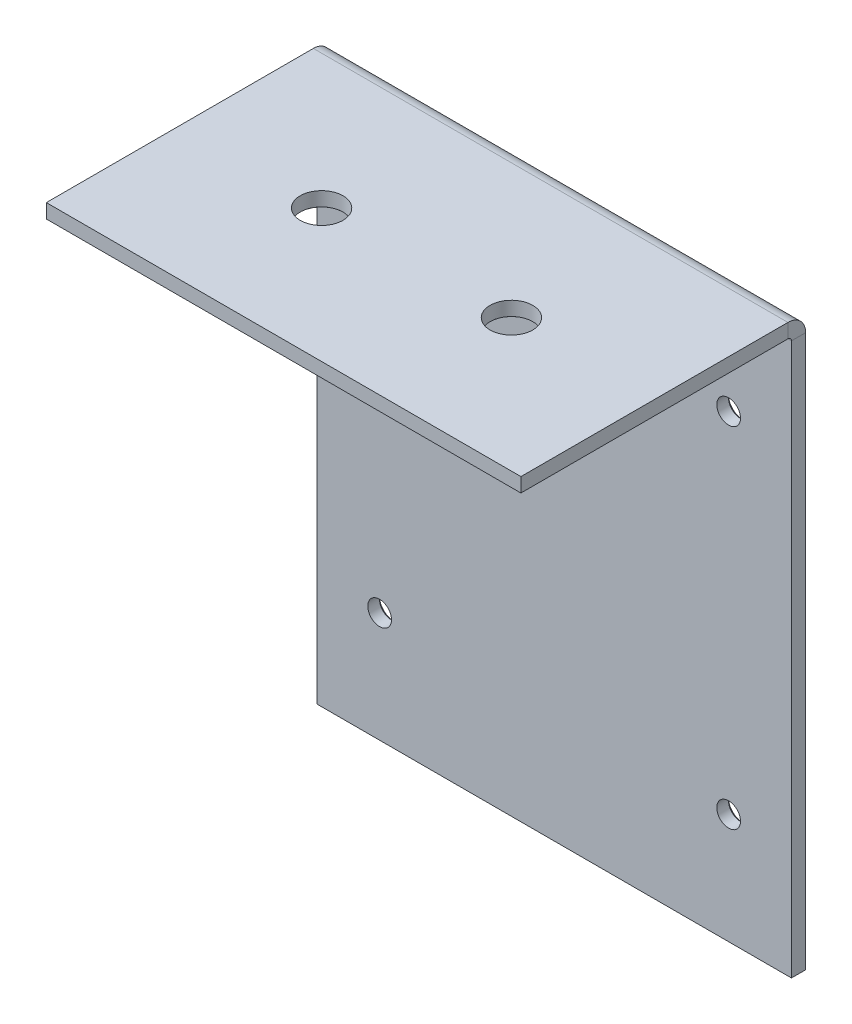
SolidWorks part; units mm, degrees
note: The reader was unsure of these and kept them because the rebuilt part matched: flange length of "边线-法兰1".
material "08优质冷轧钢板"
ref_plane "前视基准面" through (0, 0, 0) normal (0, 0, 1) x (1, 0, 0)
ref_plane "上视基准面" through (0, 0, 0) normal (0, 1, 0) x (1, 0, 0)
ref_plane "右视基准面" through (0, 0, 0) normal (1, 0, 0) x (0, 0, -1)
other "Configuration Table"
sketch "草图1" plane through (0, 0, 0) normal (0, 0, 1) x (1, 0, 0)
  line L1 (-50, 60) -> (50, 60)
  line L2 (-50, 60) -> (-50, -60)
  line L3 (-50, -60) -> (50, -60)
  line L4 (50, 60) -> (50, -60)
  line L5 (-50, 60) -> (50, -60) construction
  line L6 (-50, -60) -> (50, 60) construction
  point P0 (0, 0)
  dimension "D1" = 100
  dimension "D2" = 120
base flange "基体-法兰1" sketch "草图1" thickness 3 reverse thickness direction no parameters "D1"=0.7366
edge flange "边线-法兰1" sketch "草图8" flange angle 90 flange length 60 flange position material inside bend radius 0.7366 thickness 3 relief rectangular parameters "D6"=10
sketch "草图8" plane through (0, 60, 0) normal (0, 1, 0) x (-1, 0, 0)
  line L0 (-50, 0) -> (50, 0) construction
  line L1 (-50, 0) -> (50, 0)
  line L2 (-50, 0) -> (-50, 57)
  line L3 (-50, 57) -> (50, 57)
  line L4 (50, 57) -> (50, 0)
bend "边线折弯1" bend radius 0.7366 bend angle 90 parameters "D5"=1
hole_wizard "M6 螺纹孔2" positions "草图11" profile "草图12" tap size "M6" standard "GB"
sketch "草图11" plane through (0, 0, -3) normal (0, 0, -1) x (-1, 0, 0)
  point P0 (-36.77, 36.77)
  point P3 (36.77, 36.77)
  point P6 (36.77, -36.77)
  point P9 (-36.77, -36.77)
sketch "草图12" plane through (36.77, 36.77, -3) normal (1, 0, 0) x (0, 1, 0)
  line L0 (0, 0) -> (0, 16.5022)
  line L1 (0, 16.5022) -> (2.5, 15)
  line L2 (2.5, 15) -> (2.5, 0.525)
  line L3 (2.5, 0.525) -> (3.025, 0)
  line L5 (3.025, 0) -> (0, 0)
  line L6 (-2.5, 0.525) -> (-3.025, 0) construction
  line L10 (0, 16.5022) -> (-2.5, 15) construction
  line L11 (0, -6.35) -> (0, 107.95) construction
  dimension "螺纹孔钻头直径" = 5
  dimension "螺纹孔钻头深度" = 15
  dimension "近端锥形沉头孔直径" = 6.05
  dimension "近端锥形沉头孔角度" = 90
  dimension "导头角度" = 118
cosmetic thread "孔螺纹线1"
cosmetic thread "孔螺纹线2"
cosmetic thread "孔螺纹线3"
cosmetic thread "孔螺纹线4"
hole_wizard "M8 间隙孔1" positions "草图13" profile "草图14" hole size "M8" standard "GB"
sketch "草图13" plane through (0, 57, 0) normal (0, -1, 0) x (-1, 0, 0)
  line L0 (0, 0) -> (0, -61.2615) construction
  line L2 (50, -57) -> (-50, -57) construction
  point P0 (20, -29)
  point P7 (-20, -29)
  point P12 (-18.9545, -40.7606)
  dimension "D1" = 40
  dimension "D2" = 28
sketch "草图14" plane through (-20, 57, 29) normal (1, 0, 0) x (0, 0, -1)
  line L0 (0, 0) -> (0, 17.7039)
  line L1 (0, 17.7039) -> (4.5, 15)
  line L2 (4.5, 15) -> (4.5, 0.025)
  line L3 (4.5, 0.025) -> (4.525, 0)
  line L5 (4.525, 0) -> (0, 0)
  line L6 (-4.5, 0.025) -> (-4.525, 0) construction
  line L10 (0, 17.7039) -> (-4.5, 15) construction
  line L11 (0, -6.35) -> (0, 107.95) construction
  dimension "孔直径" = 9
  dimension "孔深度" = 15
  dimension "近端锥形沉头孔直径" = 9.05
  dimension "近端锥形沉头孔角度" = 90
  dimension "导头角度" = 118
sketch "折弯-线1" [suppressed] plane through (0, 0, 0) normal (0, 1, 0) x (1, 0, 0)
sketch "边界框1" [suppressed] plane through (0, 0, 0) normal (0, 1, 0) x (1, 0, 0)
sheet metal parameters "钣金6" thickness 3 parameters "D1"=0.7366
flat pattern "平板型式6" [suppressed]
sketch "折弯-线2" plane through (0, 0, 0) normal (0, 1, 0) x (1, 0, 0)
sketch "边界框2" [suppressed] plane through (0, 0, 0) normal (0, 1, 0) x (1, 0, 0)
sheet metal parameters "钣金7" thickness 3 parameters "D1"=0.7366
flat pattern "平板型式6"
sketch "折弯-线2" plane through (0, 0, 0) normal (0, 0, 1) x (1, 0, 0)
  line L0 (50, 58.02) -> (-50, 58.02) construction
  line L1 (50, 58.02) -> (-50, 58.02) construction
sketch3d "边界框2" [suppressed]
  line L0 (50, 116.04, 0) -> (50, -60, 0) construction
  line L1 (-50, 116.04, 0) -> (-50, -60, 0) construction
  line L2 (50, 116.04, 0) -> (-50, 116.04, 0) construction
  line L3 (50, -60, 0) -> (-50, -60, 0) construction
bend of the flat pattern "展平-<边线折弯1>1"
sheet metal parameters "钣金8" thickness 3 parameters "D1"=0.7366
flat pattern "平板型式6"
sketch "折弯-线2" plane through (0, 0, 0) normal (0, 0, 1) x (1, 0, 0)
  line L0 (50, 58.02) -> (-50, 58.02) construction
  line L1 (50, 58.02) -> (-50, 58.02) construction
sketch3d "边界框2" [suppressed]
  line L0 (50, 116.04, 0) -> (50, -60, 0) construction
  line L1 (-50, 116.04, 0) -> (-50, -60, 0) construction
  line L2 (50, 116.04, 0) -> (-50, 116.04, 0) construction
  line L3 (50, -60, 0) -> (-50, -60, 0) construction
bend of the flat pattern "展平-<边线折弯1>1"
sheet metal parameters "钣金9" thickness 3 parameters "D1"=0.7366
flat pattern "平板型式6"
sketch "折弯-线2" plane through (0, 0, 0) normal (0, 0, 1) x (1, 0, 0)
  line L0 (50, 58.02) -> (-50, 58.02) construction
  line L1 (50, 58.02) -> (-50, 58.02) construction
sketch3d "边界框2" [suppressed]
  line L0 (50, 116.04, 0) -> (50, -60, 0) construction
  line L1 (-50, 116.04, 0) -> (-50, -60, 0) construction
  line L2 (50, 116.04, 0) -> (-50, 116.04, 0) construction
  line L3 (50, -60, 0) -> (-50, -60, 0) construction
bend of the flat pattern "展平-<边线折弯1>1"
